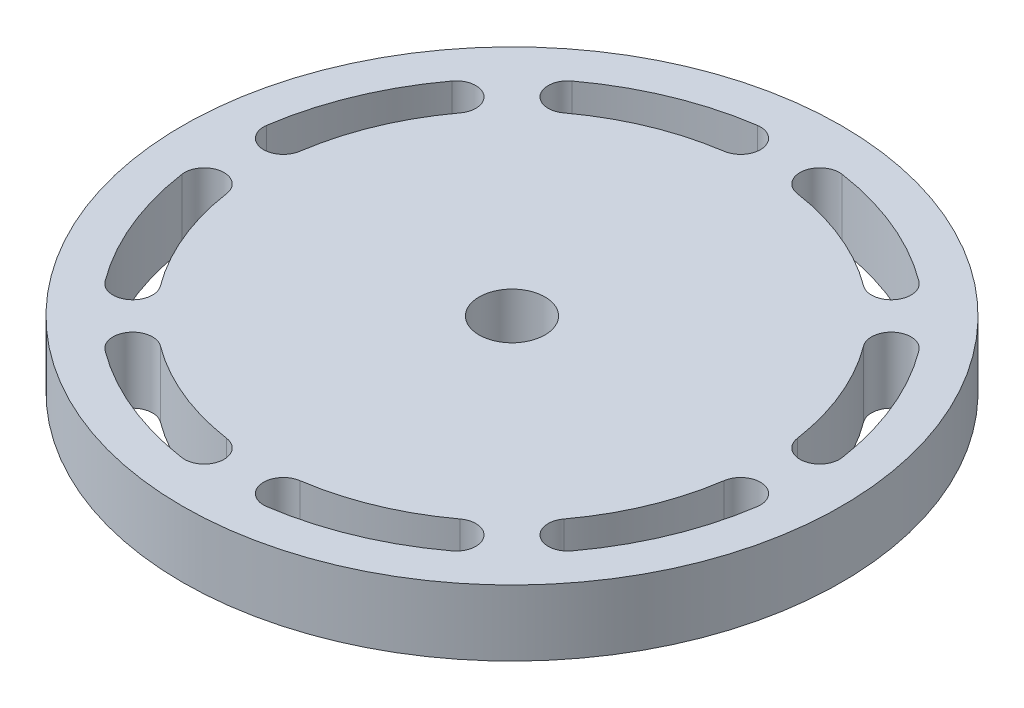
SolidWorks part; units mm, degrees
ref_plane "Front Plane" through (0, 0, 0) normal (0, 0, 1) x (1, 0, 0)
ref_plane "Top Plane" through (0, 0, 0) normal (0, 1, 0) x (1, 0, 0)
ref_plane "Right Plane" through (0, 0, 0) normal (1, 0, 0) x (0, 0, -1)
sketch "Sketch1" plane through (0, 0, 0) normal (0, 1, 0) x (1, 0, 0)
  line L4 (44.7892, 14.5529) -> (0, 47.0942) construction
  line L5 (0, 47.0942) -> (-44.7892, 14.5529) construction
  line L9 (-44.7892, 14.5529) -> (-27.6813, -38.1) [skipped]
  line L10 (-27.6813, -38.1) -> (27.6813, -38.1) [skipped]
  line L11 (27.6813, -38.1) -> (44.7892, 14.5529) [skipped]
  line L14 (-31.5904, -3.1799) -> (-27.8167, -15.3066) construction
  circle A0 centre (0, 0) radius 31.75
  dimension "D1" = 63.5
extrude "Boss-Extrude1" add sketch "Sketch1" along normal blind 6.35
sketch "Sketch2" plane through (0, 6.35, 0) normal (0, 1, 0) x (1, 0, 0)
  circle A0 centre (0, 0) radius 3.175
  dimension "D1" = 6.35
extrude "Cut-Extrude1" cut sketch "Sketch2" against normal through all
sketch "Sketch3" plane through (0, 6.35, 0) normal (0, 1, 0) x (1, 0, 0)
  line L0 (0, 0) -> (0, -31.75) construction
  line L1 (0, -31.75) -> (0, 31.75) construction
  line L2 (0, 31.75) -> (0, 0) construction
  line L3 (0, 0) -> (31.75, 0) construction
  line L4 (31.75, 0) -> (-31.75, 0) construction
  line L5 (-31.75, 0) -> (0, 0) construction
  line L6 (0, 0) -> (22.4506, -22.4506) construction
  line L7 (0, 0) -> (-22.4506, 22.4506) construction
  line L8 (-22.4506, 22.4506) -> (0, 0) construction
  line L9 (0, 0) -> (22.4506, 22.4506) construction
  line L10 (22.4506, 22.4506) -> (-22.4506, -22.4506) construction
  arc A0 (-15.5767, 20.9648) -> (-3.81, 25.8387) centre (0, 0) cw construction
  arc A1 (-4.0879, 27.7234) -> (-16.7128, 22.494) centre (0, 0) ccw
  arc A2 (-3.5321, 23.9541) -> (-14.4405, 19.4357) centre (0, 0) ccw
  arc A3 (-3.5321, 23.9541) -> (-4.0879, 27.7234) centre (-3.81, 25.8387) ccw
  arc A4 (-16.7128, 22.494) -> (-14.4405, 19.4357) centre (-15.5767, 20.9648) ccw
  circle A5 centre (0, 0) radius 31.75 construction
  arc A6 (-20.9648, 15.5767) -> (-25.8387, 3.81) centre (0, 0) ccw construction
  arc A7 (-27.7234, 4.0879) -> (-22.494, 16.7128) centre (0, 0) cw
  arc A8 (-23.9541, 3.5321) -> (-19.4357, 14.4405) centre (0, 0) cw
  arc A9 (-23.9541, 3.5321) -> (-27.7234, 4.0879) centre (-25.8387, 3.81) cw
  arc A10 (-22.494, 16.7128) -> (-19.4357, 14.4405) centre (-20.9648, 15.5767) cw
  arc A11 (-20.9648, -15.5767) -> (-25.8387, -3.81) centre (0, 0) cw construction
  arc A12 (-27.7234, -4.0879) -> (-22.494, -16.7128) centre (0, 0) ccw
  arc A13 (-23.9541, -3.5321) -> (-19.4357, -14.4405) centre (0, 0) ccw
  arc A14 (-23.9541, -3.5321) -> (-27.7234, -4.0879) centre (-25.8387, -3.81) ccw
  arc A15 (-22.494, -16.7128) -> (-19.4357, -14.4405) centre (-20.9648, -15.5767) ccw
  arc A16 (-15.5767, -20.9648) -> (-3.81, -25.8387) centre (0, 0) ccw construction
  arc A17 (-4.0879, -27.7234) -> (-16.7128, -22.494) centre (0, 0) cw
  arc A18 (-3.5321, -23.9541) -> (-14.4405, -19.4357) centre (0, 0) cw
  arc A19 (-3.5321, -23.9541) -> (-4.0879, -27.7234) centre (-3.81, -25.8387) cw
  arc A20 (-16.7128, -22.494) -> (-14.4405, -19.4357) centre (-15.5767, -20.9648) cw
  arc A21 (15.5767, -20.9648) -> (3.81, -25.8387) centre (0, 0) cw construction
  arc A22 (4.0879, -27.7234) -> (16.7128, -22.494) centre (0, 0) ccw
  arc A23 (3.5321, -23.9541) -> (14.4405, -19.4357) centre (0, 0) ccw
  arc A24 (3.5321, -23.9541) -> (4.0879, -27.7234) centre (3.81, -25.8387) ccw
  arc A25 (16.7128, -22.494) -> (14.4405, -19.4357) centre (15.5767, -20.9648) ccw
  arc A26 (20.9648, -15.5767) -> (25.8387, -3.81) centre (0, 0) ccw construction
  arc A27 (27.7234, -4.0879) -> (22.494, -16.7128) centre (0, 0) cw
  arc A28 (23.9541, -3.5321) -> (19.4357, -14.4405) centre (0, 0) cw
  arc A29 (23.9541, -3.5321) -> (27.7234, -4.0879) centre (25.8387, -3.81) cw
  arc A30 (22.494, -16.7128) -> (19.4357, -14.4405) centre (20.9648, -15.5767) cw
  arc A31 (20.9648, 15.5767) -> (25.8387, 3.81) centre (0, 0) cw construction
  arc A32 (27.7234, 4.0879) -> (22.494, 16.7128) centre (0, 0) ccw
  arc A33 (23.9541, 3.5321) -> (19.4357, 14.4405) centre (0, 0) ccw
  arc A34 (23.9541, 3.5321) -> (27.7234, 4.0879) centre (25.8387, 3.81) ccw
  arc A35 (22.494, 16.7128) -> (19.4357, 14.4405) centre (20.9648, 15.5767) ccw
  arc A36 (15.5767, 20.9648) -> (3.81, 25.8387) centre (0, 0) ccw construction
  arc A37 (4.0879, 27.7234) -> (16.7128, 22.494) centre (0, 0) cw
  arc A38 (3.5321, 23.9541) -> (14.4405, 19.4357) centre (0, 0) cw
  arc A39 (3.5321, 23.9541) -> (4.0879, 27.7234) centre (3.81, 25.8387) cw
  arc A40 (16.7128, 22.494) -> (14.4405, 19.4357) centre (15.5767, 20.9648) cw
  point P4 (-9.995, 24.13)
  point P16 (0, 0)
  point P24 (-24.13, 9.995)
  point P31 (-24.13, -9.995)
  point P38 (-9.995, -24.13)
  point P45 (9.995, -24.13)
  point P52 (24.13, -9.995)
  point P59 (24.13, 9.995)
  point P66 (9.995, 24.13)
  dimension "D2" = 3.81
  dimension "D1" = 24.13
  dimension "D3" = 3.81
  dimension "D4" = 3.81
  dimension "D5" = 45
extrude "Cut-Extrude2" cut sketch "Sketch3" against normal through all
